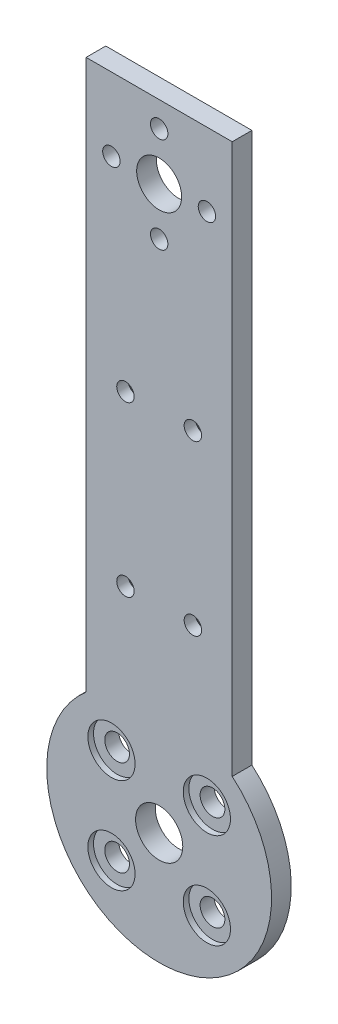
SolidWorks part; units mm, degrees
ref_plane "Front Plane" through (0, 0, 0) normal (0, 0, 1) x (1, 0, 0)
ref_plane "Top Plane" through (0, 0, 0) normal (0, 1, 0) x (1, 0, 0)
ref_plane "Right Plane" through (0, 0, 0) normal (1, 0, 0) x (0, 0, -1)
sketch "Sketch1" plane through (0, 0, 0) normal (0, 0, 1) x (1, 0, 0)
  line L2 (13, 113) -> (-13, 113)
  line L4 (0, 0) -> (8.4853, 8.4853) construction
  line L5 (0, 0) -> (0, 100) construction
  line L6 (0, 0) -> (0, 35) construction
  line L7 (6, 35) -> (-6, 35) construction
  line L8 (0, 100) -> (0, 65) construction
  line L9 (-6, 65) -> (6, 65) construction
  line L13 (-13, 113) -> (-13, 15.1987)
  line L14 (13, 113) -> (13, 15.1987)
  circle A2 centre (0, 0) radius 12 construction
  circle A3 centre (8.4853, 8.4853) radius 2.2
  circle A4 centre (8.4853, -8.4853) radius 2.2
  circle A5 centre (-8.4853, -8.4853) radius 2.2
  circle A6 centre (-8.4853, 8.4853) radius 2.2
  circle A7 centre (0, 0) radius 4.2
  circle A8 centre (0, 100) radius 4
  circle A9 centre (0, 100) radius 8.5 construction
  circle A10 centre (0, 108.5) radius 1.55
  circle A11 centre (8.5, 100) radius 1.55
  circle A12 centre (0, 91.5) radius 1.55
  circle A13 centre (-8.5, 100) radius 1.55
  circle A14 centre (6, 65) radius 1.55
  circle A15 centre (6, 35) radius 1.55
  circle A16 centre (-6, 65) radius 1.55
  circle A17 centre (-6, 35) radius 1.55
  circle A19 centre (0, 0) radius 20 construction
  arc A22 (-13, 15.1987) -> (13, 15.1987) centre (0, 0) ccw
  point P6 (0, 0)
  point P19 (0, 0)
  point P31 (0, 100)
  point P33 (0, 35)
  point P38 (0, 65)
  dimension "D1" = 4
  dimension "D2" = 4
extrude "Boss-Extrude1" add sketch "Sketch1" along normal blind 3.5
sketch "Sketch3" plane through (0, 0, 3.5) normal (0, 0, 1) x (1, 0, 0)
  circle A0 centre (-8.4853, 8.4853) radius 4.2
  circle A4 centre (8.4853, 8.4853) radius 4.2
  circle A5 centre (8.4853, -8.4853) radius 4.2
  circle A6 centre (-8.4853, -8.4853) radius 4.2
  point P12 (0, 0)
  dimension "D1" = 4
extrude "Cut-Extrude1" cut sketch "Sketch3" against normal blind 1
sketch "Sketch4" plane through (0, 0, 0) normal (0, 0, -1) x (-1, 0, 0)
  circle A0 centre (-6, 35) radius 3.5
  circle A1 centre (6, 35) radius 3.5
  circle A2 centre (-6, 65) radius 3.5
  circle A3 centre (6, 65) radius 3.5
extrude "Cut-Extrude2" cut sketch "Sketch4" against normal blind 1.5
